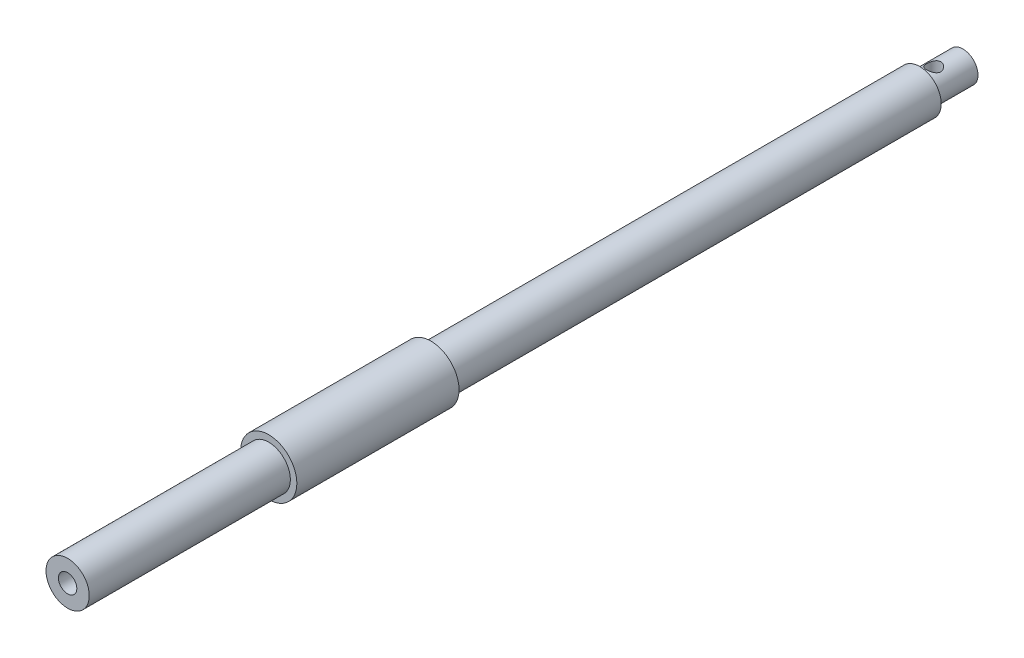
SolidWorks part; units mm, degrees
material "Structural Steel"
ref_plane "Piano frontale" through (0, 0, 0) normal (0, 0, 1) x (1, 0, 0)
ref_plane "Piano superiore" through (0, 0, 0) normal (0, 1, 0) x (1, 0, 0)
ref_plane "Piano destro" through (0, 0, 0) normal (1, 0, 0) x (0, 0, -1)
sketch "Schizzo1" plane through (0, 0, 0) normal (0, 0, 1) x (1, 0, 0)
  circle A0 centre (0, 0) radius 7
  dimension "D1" = 14
extrude "Estrusione1" add sketch "Schizzo1" along normal blind 20
sketch "Schizzo2" plane through (0, 0, 20) normal (0, 0, 1) x (1, 0, 0)
  circle A0 centre (0, 0) radius 10
  dimension "D1" = 20
extrude "Estrusione2" add sketch "Schizzo2" along normal blind 226
sketch "Schizzo6" plane through (0, 0, 246) normal (0, 0, 1) x (1, 0, 0)
  circle A0 centre (0, 0) radius 13
  dimension "D1" = 26
extrude "Estrusione-Estrusione1" add sketch "Schizzo6" along normal blind 75
sketch "Schizzo7" plane through (0, 0, 321) normal (0, 0, 1) x (1, 0, 0)
  circle A0 centre (0, 0) radius 10
  dimension "D1" = 20
extrude "Estrusione-Estrusione2" add sketch "Schizzo7" along normal blind 93
hole_wizard "Foro filettato M10-1" positions "Schizzo9" profile "Schizzo8" tap size "M10" standard "ISO"
sketch "Schizzo9" plane through (0, 0, 414) normal (0, 0, 1) x (1, 0, 0)
  point P0 (0, 0)
sketch "Schizzo8" plane through (0, 0, 414) normal (1, 0, 0) x (0, -1, 0)
  line L0 (0, 0) -> (0, 30.0537)
  line L1 (0, 30.0537) -> (4.25, 27.5)
  line L2 (4.25, 27.5) -> (4.25, 0)
  line L5 (4.25, 0) -> (0, 0)
  line L10 (0, 30.0537) -> (-4.25, 27.5) construction
  line L11 (0, -6.35) -> (0, 107.95) construction
  dimension "Tap Drill Dia." = 8.5
  dimension "Tap Drill Depth" = 27.5
  dimension "Drill Angle" = 118
cosmetic thread "Filettatura del foro1" parameters "D1"=20, "D2"=10
sketch "Schizzo10" plane through (0, 0, 0) normal (0, 1, 0) x (1, 0, 0)
  line L0 (0, -1000) -> (0, 49000) construction
  line L1 (10, -20) -> (-10, -20) construction
  circle A0 centre (0, -13.5) radius 3.25
  dimension "D1" = 6.5
  dimension "D2" = 6.5
extrude "Taglio-Estrusione1" cut sketch "Schizzo10" against normal blind 10 and the other way blind 10
